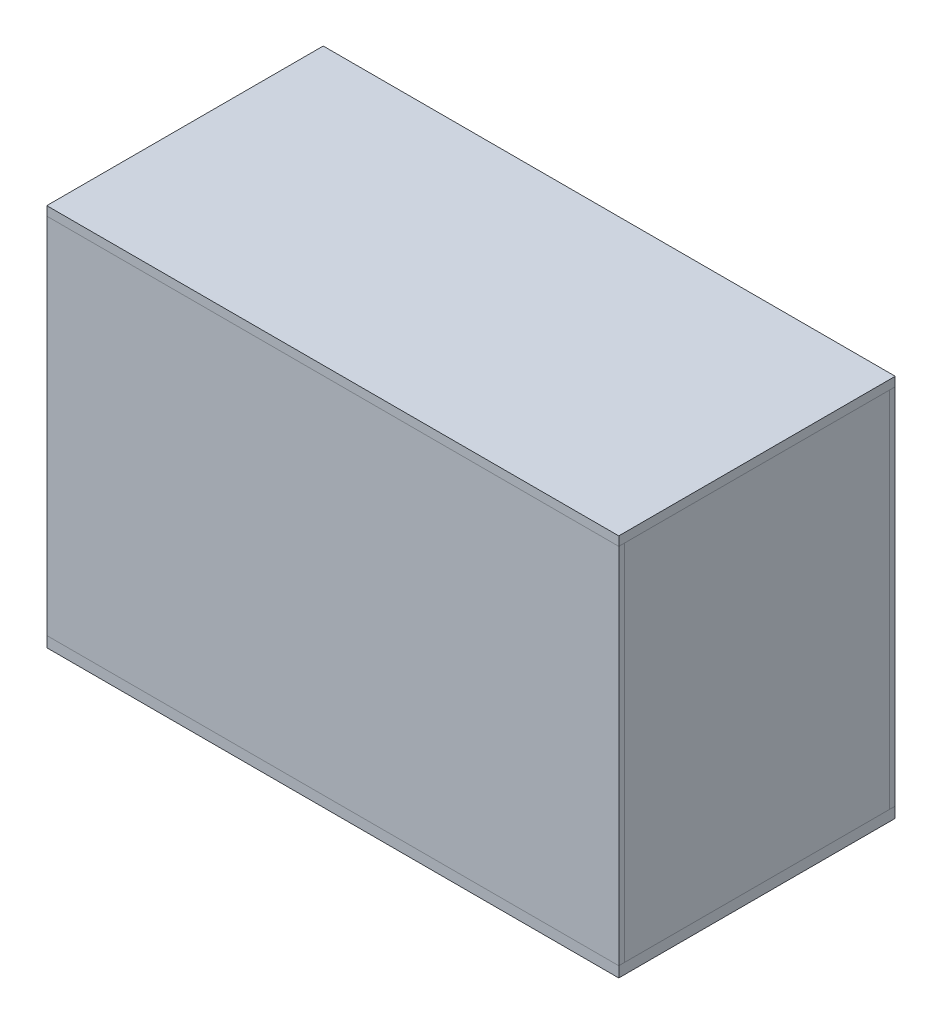
SolidWorks part; units mm, degrees
material "Acrylic (Medium-high impact)"
ref_plane "Front" through (0, 0, 0) normal (0, 0, 1) x (1, 0, 0)
ref_plane "Top" through (0, 0, 0) normal (0, 1, 0) x (1, 0, 0)
ref_plane "Right" through (0, 0, 0) normal (1, 0, 0) x (0, 0, -1)
sketch "Sketch1" plane through (0, 0, 0) normal (0, 1, 0) x (1, 0, 0)
  line L1 (-80.01, 38.6715) -> (80.01, 38.6715)
  line L2 (-80.01, 38.6715) -> (-80.01, -38.6715)
  line L3 (-80.01, -38.6715) -> (80.01, -38.6715)
  line L4 (80.01, 38.6715) -> (80.01, -38.6715)
  line L5 (-80.01, 38.6715) -> (80.01, -38.6715) construction
  line L6 (-80.01, -38.6715) -> (80.01, 38.6715) construction
  point P0 (0, 0)
  dimension "D1" = 77.343
  dimension "D2" = 160.02
extrude "Boss-Extrude1" add sketch "Sketch1" along normal blind 2.54
sketch "Sketch2" plane through (0, 2.54, 0) normal (0, 1, 0) x (1, 0, 0)
  line L0 (80.01, -38.6715) -> (80.01, 38.6715) construction
  line L1 (-70.485, 29.1465) -> (70.485, 29.1465) construction
  line L2 (-70.485, 29.1465) -> (-70.485, -29.1465) construction
  line L3 (-70.485, -29.1465) -> (70.485, -29.1465) construction
  line L4 (70.485, 29.1465) -> (70.485, -29.1465) construction
  line L5 (-70.485, 29.1465) -> (70.485, -29.1465) construction
  line L6 (-70.485, -29.1465) -> (70.485, 29.1465) construction
  line L7 (80.01, 38.6715) -> (-80.01, 38.6715) construction
  line L9 (-70.485, 29.1465) -> (-69.215, 29.1465)
  line L10 (-70.485, 29.1465) -> (-70.485, 27.8765)
  line L11 (-70.485, 27.8765) -> (-69.215, 27.8765)
  line L12 (-69.215, 29.1465) -> (-69.215, 27.8765)
  point P0 (0, 0)
  dimension "D1" = 9.525
  dimension "D2" = 9.525
  dimension "D3" = 1.27
  dimension "D4" = 1.27
extrude "Cut-Extrude1" [suppressed] cut sketch "Sketch2" against normal through all
pattern_linear "LPattern1" [suppressed] count 71 spacing 1.905 count 29 spacing 1.905 of bodies 180
sketch "Sketch3" [suppressed] plane through (0, 2.54, 0) normal (0, 1, 0) x (1, 0, 0)
  line L1 (-70.485, 29.1465) -> (64.135, 29.1465)
  line L2 (-70.485, 29.1465) -> (-70.485, -25.4635)
  line L3 (-70.485, -25.4635) -> (64.135, -25.4635)
  line L4 (64.135, 29.1465) -> (64.135, -25.4635)
extrude "Cut-Extrude2" [suppressed] cut sketch "Sketch3" against normal through all
sketch "WALL THICKNESS CONTROL" plane through (0, 0, 0) normal (0, -1, 0) x (1, 0, 0)
  line L0 (80.01, 38.6715) -> (80.01, -38.6715) construction
  line L1 (-80.01, 38.6715) -> (80.01, 38.6715)
  line L2 (-80.01, 38.6715) -> (-80.01, 37.084)
  line L3 (-80.01, 37.084) -> (80.01, 37.084)
  line L4 (80.01, 38.6715) -> (80.01, 37.084)
  line L5 (78.4225, 0) -> (80.01, 0) construction
  line L6 (-80.01, -38.6715) -> (80.01, -38.6715)
  line L7 (-80.01, -38.6715) -> (-80.01, -37.084)
  line L8 (-80.01, -37.084) -> (80.01, -37.084)
  line L9 (80.01, -38.6715) -> (80.01, -37.084)
  line L10 (80.01, 37.084) -> (78.4225, 37.084)
  line L11 (80.01, 37.084) -> (80.01, -37.084)
  line L12 (80.01, -37.084) -> (78.4225, -37.084)
  line L13 (78.4225, 37.084) -> (78.4225, -37.084)
  line L14 (-80.01, 37.084) -> (-78.4225, 37.084)
  line L15 (-80.01, 37.084) -> (-80.01, -37.084)
  line L16 (-80.01, -37.084) -> (-78.4225, -37.084)
  line L17 (-78.4225, 37.084) -> (-78.4225, -37.084)
  line L18 (-78.4225, 0) -> (-80.01, 0) construction
  dimension "D1" = 1.5875
sketch "Sketch5" plane through (0, 0, 0) normal (0, -1, 0) x (1, 0, 0)
  line L0 (-80.01, -37.084) -> (80.01, -37.084) construction
  line L1 (80.01, -38.6715) -> (80.01, -37.084) construction
  line L2 (-80.01, -38.6715) -> (80.01, -38.6715) construction
  line L3 (-80.01, -38.6715) -> (-80.01, -37.084) construction
  line L12 (-80.01, 37.084) -> (80.01, 37.084) construction
  line L13 (80.01, 38.6715) -> (80.01, 37.084) construction
  line L14 (-80.01, 38.6715) -> (80.01, 38.6715) construction
  line L15 (-80.01, 38.6715) -> (-80.01, 37.084) construction
  line L16 (-80.01, -37.084) -> (80.01, -37.084)
  line L17 (80.01, -38.6715) -> (80.01, -37.084)
  line L18 (-80.01, -38.6715) -> (80.01, -38.6715)
  line L19 (-80.01, -38.6715) -> (-80.01, -37.084)
  line L28 (-80.01, 37.084) -> (80.01, 37.084)
  line L29 (80.01, 38.6715) -> (80.01, 37.084)
  line L30 (-80.01, 38.6715) -> (80.01, 38.6715)
  line L31 (-80.01, 38.6715) -> (-80.01, 37.084)
extrude "Boss-Extrude2" add sketch "Sketch5" along normal blind 101.6 separate body
sketch "Sketch6" plane through (0, 0, 0) normal (0, -1, 0) x (1, 0, 0)
  line L4 (80.01, 37.084) -> (80.01, -37.084) construction
  line L5 (80.01, 37.084) -> (78.4225, 37.084) construction
  line L6 (78.4225, 37.084) -> (78.4225, -37.084) construction
  line L7 (80.01, -37.084) -> (78.4225, -37.084) construction
  line L8 (-80.01, 37.084) -> (-80.01, -37.084) construction
  line L9 (-80.01, 37.084) -> (-78.4225, 37.084) construction
  line L10 (-78.4225, 37.084) -> (-78.4225, -37.084) construction
  line L11 (-80.01, -37.084) -> (-78.4225, -37.084) construction
  line L20 (80.01, 37.084) -> (80.01, -37.084)
  line L21 (80.01, 37.084) -> (78.4225, 37.084)
  line L22 (78.4225, 37.084) -> (78.4225, -37.084)
  line L23 (80.01, -37.084) -> (78.4225, -37.084)
  line L24 (-80.01, 37.084) -> (-80.01, -37.084)
  line L25 (-80.01, 37.084) -> (-78.4225, 37.084)
  line L26 (-78.4225, 37.084) -> (-78.4225, -37.084)
  line L27 (-80.01, -37.084) -> (-78.4225, -37.084)
extrude "Boss-Extrude3" add sketch "Sketch6" along normal up to surface (101.6 mm away) separate body up to face at (0, -101.6, 37.8777)
sketch "Sketch7" plane through (0, -101.6, 0) normal (0, -1, 0) x (1, 0, 0)
  line L1 (-80.01, 38.6715) -> (80.01, 38.6715)
  line L2 (-80.01, 38.6715) -> (-80.01, -38.6715)
  line L3 (-80.01, -38.6715) -> (80.01, -38.6715)
  line L4 (80.01, 38.6715) -> (80.01, -38.6715)
extrude "Boss-Extrude4" add sketch "Sketch7" along normal blind 2.9718 separate body
sketch "Sketch14" plane through (0, 0, -38.6715) normal (0, 0, -1) x (-1, 0, 0)
  line L0 (80.01, -101.6) -> (-80.01, -101.6) construction
  line L1 (-78.6543, -50.8) -> (78.7234, -50.8)
  line L2 (-78.6543, -50.8) -> (-78.6543, -53.975)
  line L3 (-78.6543, -53.975) -> (78.7234, -53.975)
  line L4 (78.7234, -50.8) -> (78.7234, -53.975)
  line L5 (80.01, -101.6) -> (-80.01, -101.6) construction
  dimension "D1" = 47.625
  dimension "D2" = 50.8
sketch "Sketch9" plane through (0, 2.54, 0) normal (0, 1, 0) x (1, 0, 0)
  line L0 (-68.0725, 33.084) -> (-68.0725, 37.084) construction
  line L1 (-74.4225, 26.734) -> (-78.4225, 26.734) construction
  line L2 (80.01, 37.084) -> (-80.01, 37.084) construction
  line L3 (-78.4225, 37.084) -> (-78.4225, -37.084) construction
  circle A0 centre (-68.0725, 26.734) radius 6.35
  dimension "D1" = 12.7
  dimension "D2" = 4
  dimension "D3" = 4
extrude "Cut-Extrude4" [suppressed] cut sketch "Sketch9" against normal through all
sketch "Sketch13" plane through (0, 0, -38.6715) normal (0, 0, -1) x (-1, 0, 0)
  line L0 (0, 0) -> (0, -101.6) construction
  line L1 (80.01, 0) -> (-80.01, 0) construction
  line L2 (80.01, -101.6) -> (-80.01, -101.6) construction
  line L3 (-52.3875, -36) -> (52.3875, -36) construction
  circle A0 centre (-52.3875, -36) radius 3.175
  circle A1 centre (52.3875, -36) radius 3.175
  point P8 (0, -36)
  dimension "D2" = 6.35
  dimension "D1" = 104.775
  dimension "D3" = 36
extrude "Cut-Extrude7" [suppressed] cut sketch "Sketch13" against normal blind 2.9718
sketch "Sketch11" plane through (0, 0, -38.6715) normal (0, 0, 1) x (1, 0, 0)
  line L0 (0, 0) -> (0, -17.78) construction
  line L1 (0, -17.78) -> (-30, -17.78) construction
  line L2 (0, -17.78) -> (30, -17.78) construction
  line L5 (-80.01, 0) -> (80.01, 0) construction
  line L6 (80.01, -101.6) -> (80.01, 0) construction
  line L7 (0, 0) -> (0, -98.425) construction
  line L8 (-52.3875, -17.78) -> (52.3875, -17.78) construction
  line L9 (-80.01, 0) -> (80.01, 0) construction
  line L10 (-80.01, -101.6) -> (-80.01, 0) construction
  line L11 (-80.01, -104.5718) -> (80.01, -104.5718) construction
  circle A0 centre (-30, -17.78) radius 7.366
  circle A1 centre (30, -17.78) radius 7.366
  circle A2 centre (60.96, -47.625) radius 7.112
  circle A3 centre (-64.135, -44.2468) radius 7.112
  circle A4 centre (-52.3875, -17.78) radius 3.175
  circle A5 centre (52.3875, -17.78) radius 3.175
  point P19 (0, -17.78)
  dimension "D1" = 14.732
  dimension "D4" = 14.224
  dimension "D6" = 19.05
  dimension "D5" = 47.625
  dimension "D8" = 6.35
  dimension "D10" = 60.325
  dimension "D11" = 15.875
  dimension "D2" = 60
  dimension "D3" = 17.78
  dimension "D7" = 104.775
  dimension "D9" = 17.78
extrude "Cut-Extrude5" cut sketch "Sketch11" along normal up to next (1.5875 mm away)
